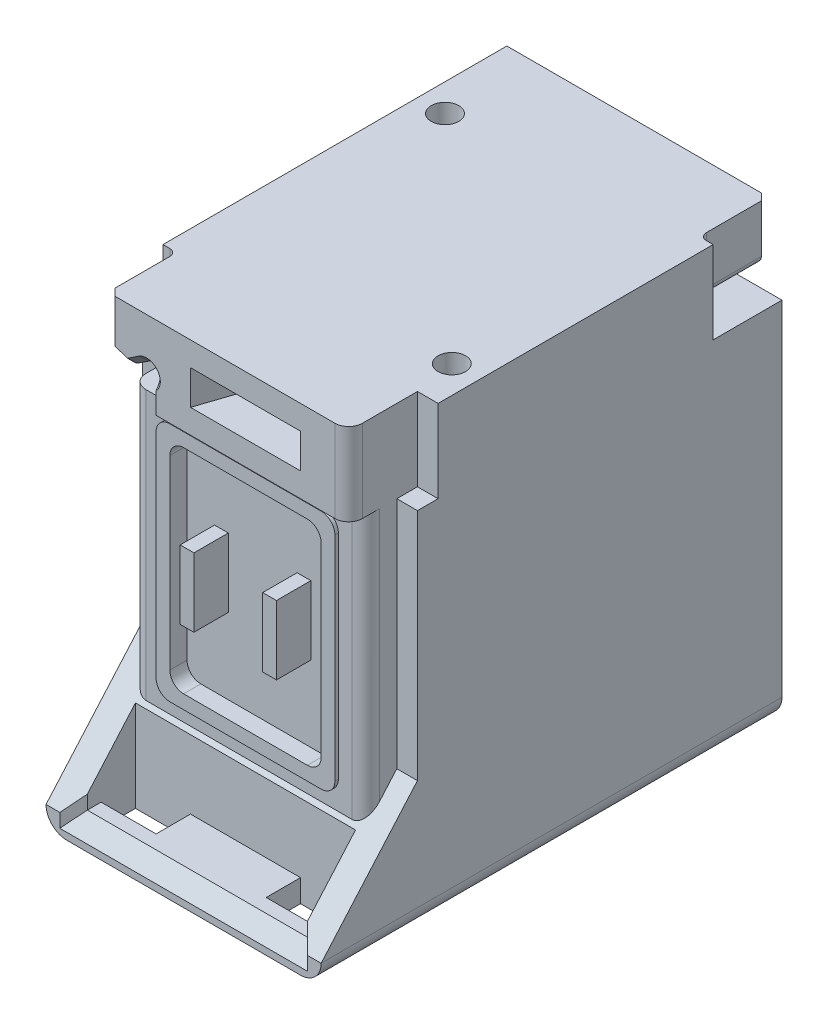
SolidWorks part; units mm, degrees
note: '?' marks a value the reader was unsure of.
ref_plane "Front Plane" through (0, 0, 0) normal (0, 0, 1) x (1, 0, 0)
ref_plane "Top Plane" through (0, 0, 0) normal (0, 1, 0) x (1, 0, 0)
ref_plane "Right Plane" through (0, 0, 0) normal (1, 0, 0) x (0, 0, -1)
sketch "Sketch1" plane through (0, 0, 0) normal (0, 0, 1) x (1, 0, 0)
  line L1 (0, 0) -> (10.16, 0)
  line L2 (0, 0) -> (0, 16.51)
  line L3 (0, 16.51) -> (10.16, 16.51)
  line L4 (10.16, 0) -> (10.16, 16.51)
  dimension "D1" = 16.51
  dimension "D2" = 10.16
extrude "Boss-Extrude1" add sketch "Sketch1" against normal blind 12.7
sketch "Sketch2" plane through (0, 0, 0) normal (-1, 0, 0) x (0, 0, 1)
  line L0 (0, 13.462) -> (0.762, 13.462)
  line L1 (0, 16.51) -> (0, 0) construction
  line L2 (0.762, 13.462) -> (0.762, 4.826)
  line L3 (0, 0) -> (4.318, 0)
  line L4 (4.318, 0) -> (4.318, 0.762)
  line L5 (4.318, 0.762) -> (0.762, 4.826)
  line L6 (0, 0) -> (0, 13.462)
  dimension "D1" = 0.762
  dimension "D2" = 8.636
  dimension "D3" = 3.048
  dimension "D4" = 4.318
  dimension "D5" = 0.762
extrude "Boss-Extrude2" add sketch "Sketch2" against normal blind 10.16
sketch "Sketch3" plane through (0, 0, -12.7) normal (0, 0, -1) x (-1, 0, 0)
  line L0 (-1.016, 4.064) -> (-2.286, 4.064)
  line L1 (-2.286, 4.064) -> (-2.286, 7.112)
  line L2 (-2.286, 7.112) -> (-1.016, 7.112)
  line L3 (-1.016, 7.112) -> (-1.016, 4.064)
  line L4 (0, 16.51) -> (0, 0) construction
  line L5 (0, 0) -> (-10.16, 0) construction
  dimension "D1" = 3.048
  dimension "D2" = 1.27
  dimension "D3" = 1.016
  dimension "D4" = 4.064
extrude "Cut-Extrude1" cut sketch "Sketch3" against normal blind 1.524
sketch "Sketch4" plane through (0, 0, -12.7) normal (0, 0, -1) x (-1, 0, 0)
  line L0 (-10.16, 13.462) -> (-7.874, 13.462)
  line L1 (-10.16, 0) -> (-10.16, 16.51) construction
  line L2 (-10.16, 13.462) -> (-10.16, 16.51)
  line L3 (-7.874, 13.462) -> (-7.874, 14.732)
  line L4 (-10.16, 16.51) -> (-9.652, 16.51)
  line L5 (-10.16, 16.51) -> (0, 16.51) construction
  line L6 (-9.652, 16.51) -> (-9.652, 14.732)
  line L7 (-9.652, 14.732) -> (-9.3225, 14.732) construction
  line L8 (-9.4681, 14.4879) -> (-9.2239, 14.4178)
  line L9 (-9.0453, 14.4323) -> (-8.3564, 14.758)
  arc A0 (-9.652, 14.732) -> (-9.4681, 14.4879) centre (-9.398, 14.732) ccw
  arc A1 (-9.2239, 14.4178) -> (-9.0453, 14.4323) centre (-9.1539, 14.6619) ccw
  arc A2 (-8.3564, 14.758) -> (-7.874, 14.732) centre (-8.1393, 14.2988) cw
  dimension "D6" = 0.254
  dimension "D7" = 0.254
  dimension "D8" = 0.254
  dimension "D10" = 0.508
  dimension "D1" = 3.048
  dimension "D2" = 2.286
  dimension "D3" = 1.27
  dimension "D4" = 0.508
  dimension "D5" = 1.778
  dimension "D9" = 0.762
extrude "Cut-Extrude2" cut sketch "Sketch4" against normal blind 2.54
sketch "Sketch6" plane through (0, 0, 0) normal (0, -1, 0) x (-1, 0, 0)
  line L0 (-1.016, -2.032) -> (-1.016, -3.302)
  line L1 (-1.016, -3.302) -> (-3.048, -3.302)
  line L2 (-3.048, -3.302) -> (-3.048, -2.032)
  line L3 (-3.048, -2.032) -> (-1.016, -2.032)
  line L4 (-10.16, -4.318) -> (0, -4.318) construction
  line L5 (0, 12.7) -> (0, -4.318) construction
  line L6 (-5.08, -4.318) -> (-5.08, 12.7) construction
  line L7 (0, 12.7) -> (-10.16, 12.7) construction
  line L8 (-7.112, -3.302) -> (-7.112, -2.032)
  line L9 (-9.144, -3.302) -> (-7.112, -3.302)
  line L10 (-9.144, -2.032) -> (-9.144, -3.302)
  line L11 (-7.112, -2.032) -> (-9.144, -2.032)
  dimension "D1" = 1.27
  dimension "D2" = 2.032
  dimension "D3" = 1.016
  dimension "D4" = 1.016
extrude "Cut-Extrude5" cut sketch "Sketch6" against normal through all
sketch "Sketch8" plane through (0, 0, 2.032) normal (0, 0, 1) x (1, 0, 0)
  line L0 (1.016, 3.3746) -> (9.144, 3.3746)
  line L1 (3.048, 3.3746) -> (1.016, 3.3746) construction
  line L2 (9.144, 3.3746) -> (9.144, 1.3426)
  line L3 (9.144, 1.3426) -> (1.016, 1.3426)
  line L4 (1.016, 1.3426) -> (1.016, 3.3746)
  line L5 (1.016, 3.3746) -> (1.016, 0) construction
  dimension "D1" = 2.032
extrude "Cut-Extrude6" cut sketch "Sketch8" along normal blind 2.54
sketch3d "3DSketch3"
  line L0 (0.508, 0.762, 4.318) -> (0.508, 0.254, 4.318)
  line L1 (10.16, 0.762, 4.318) -> (0, 0.762, 4.318) construction
  line L2 (0, 0, 4.318) -> (0, 0.762, 4.318) construction
  line L3 (0.508, 0.762, 4.318) -> (1.016, 1.3426, 3.81)
  line L5 (1.016, 1.3426, 3.81) -> (1.016, 0.8346, 3.81)
  line L6 (1.016, 0.8346, 3.81) -> (0.508, 0.254, 4.318)
  dimension "D1" = 0.508
  dimension "D2" = 0.508
extrude "Cut-Extrude7" cut sketch "3DSketch3" along direction (-1, 0, 0) on the side against the normal blind 8.128
sketch "Sketch10" plane through (0, 0, 3.81) normal (0, 0, 1) x (1, 0, 0)
  line L1 (1.016, 0.8346) -> (9.144, 0.8346)
  line L2 (1.016, 0.8346) -> (1.016, 1.3426)
  line L3 (1.016, 1.3426) -> (9.144, 1.3426)
  line L4 (9.144, 0.8346) -> (9.144, 1.3426)
extrude "Cut-Extrude8" cut sketch "Sketch10" against normal up to surface (1.778 mm away)
sketch3d "3DSketch6"
  line L0 (9.652, 0.762, 4.318) -> (9.144, 1.3426, 3.81)
  line L1 (10.16, 0.762, 4.318) -> (8.636, 0.762, 4.318) construction
  line L2 (9.144, 1.3426, 3.81) -> (9.144, 0.8346, 3.81)
  line L3 (9.652, 0.762, 4.318) -> (9.652, 0.254, 4.318)
  line L4 (9.652, 0.254, 4.318) -> (9.144, 0.8346, 3.81)
  dimension "D1" = 0.508
extrude "Cut-Extrude9" cut sketch "3DSketch6" along direction (-1, 0, 0) on the side of the normal blind 1.778
sketch "Sketch12" plane through (0, 13.462, 0) normal (0, 1, 0) x (1, 0, 0)
  line L0 (0.762, -0.762) -> (0.762, -1.905)
  line L1 (10.16, -0.762) -> (0, -0.762) construction
  line L2 (0.762, -1.905) -> (9.398, -1.905)
  line L3 (9.398, -1.905) -> (9.398, -0.762)
  line L4 (9.398, -0.762) -> (0.762, -0.762)
  dimension "D1" = 1.143
  dimension "D2" = 0.762
  dimension "D3" = 0.762
extrude "Boss-Extrude3" add sketch "Sketch12" against normal up to surface (9.9423 mm away)
sketch "Sketch13" plane through (0, 0, 1.905) normal (0, 0, 1) x (1, 0, 0)
  line L0 (0.762, 8.4909) -> (9.398, 8.4909) construction
  line L1 (0.762, 3.5197) -> (0.762, 13.462) construction
  line L2 (9.398, 3.5197) -> (9.398, 13.462) construction
  line L3 (5.08, 13.462) -> (5.08, 3.5197) construction
  line L4 (0.762, 13.462) -> (9.398, 13.462) construction
  line L5 (9.398, 3.5197) -> (0.762, 3.5197) construction
  line L7 (2.794, 12.4279) -> (7.366, 12.4279)
  line L8 (2.286, 11.9199) -> (2.286, 5.0619)
  line L9 (2.794, 4.5539) -> (7.366, 4.5539)
  line L10 (7.874, 11.9199) -> (7.874, 5.0619)
  line L11 (2.286, 12.4279) -> (7.874, 4.5539) construction
  line L12 (2.286, 4.5539) -> (7.874, 12.4279) construction
  arc A0 (2.286, 5.0619) -> (2.794, 4.5539) centre (2.794, 5.0619) ccw
  arc A1 (7.366, 4.5539) -> (7.874, 5.0619) centre (7.366, 5.0619) ccw
  arc A2 (7.366, 12.4279) -> (7.874, 11.9199) centre (7.366, 11.9199) cw
  arc A3 (2.794, 12.4279) -> (2.286, 11.9199) centre (2.794, 11.9199) ccw
  point P12 (5.08, 8.4909)
  dimension "D2" = 0.508
  dimension "D1" = 5.588
extrude "Cut-Extrude10" cut sketch "Sketch13" against normal blind 0.508
sketch "Sketch14" plane through (0, 0, 1.905) normal (0, 0, 1) x (1, 0, 0)
  line L0 (0.762, 8.4909) -> (9.398, 8.4909) construction
  line L1 (0.762, 3.5197) -> (0.762, 13.462) construction
  line L2 (9.398, 3.5197) -> (9.398, 13.462) construction
  line L3 (5.08, 13.462) -> (5.08, 3.5197) construction
  line L4 (0.762, 13.462) -> (9.398, 13.462) construction
  line L5 (9.398, 3.5197) -> (0.762, 3.5197) construction
  line L6 (7.366, 12.4279) -> (2.794, 12.4279) construction
  line L7 (2.286, 4.0459) -> (7.874, 4.0459)
  line L8 (1.778, 4.5539) -> (1.778, 12.4279)
  line L9 (2.286, 12.9359) -> (7.874, 12.9359)
  line L10 (8.382, 4.5539) -> (8.382, 12.4279)
  line L11 (2.1862, 4.5953) -> (8.382, 12.9359) construction
  line L12 (1.778, 12.9359) -> (8.382, 4.0459) construction
  line L13 (2.286, 11.9199) -> (2.286, 5.0619) construction
  line L15 (2.794, 12.4279) -> (7.366, 12.4279)
  line L16 (2.286, 11.9199) -> (2.286, 5.0619)
  line L17 (2.794, 4.5539) -> (7.366, 4.5539)
  line L18 (7.874, 11.9199) -> (7.874, 5.0619)
  line L19 (2.286, 12.4279) -> (7.874, 4.5539) construction
  line L20 (2.286, 4.5539) -> (7.874, 12.4279) construction
  arc A0 (2.286, 4.0459) -> (1.778, 4.5539) centre (2.286, 4.5539) cw
  arc A1 (7.874, 4.0459) -> (8.382, 4.5539) centre (7.874, 4.5539) ccw
  arc A2 (7.874, 12.9359) -> (8.382, 12.4279) centre (7.874, 12.4279) cw
  arc A3 (1.778, 12.4279) -> (2.286, 12.9359) centre (2.286, 12.4279) cw
  arc A4 (2.794, 12.4279) -> (2.286, 11.9199) centre (2.794, 11.9199) ccw
  arc A5 (7.366, 12.4279) -> (7.874, 11.9199) centre (7.366, 11.9199) cw
  arc A6 (7.366, 4.5539) -> (7.874, 5.0619) centre (7.366, 5.0619) ccw
  arc A7 (2.286, 5.0619) -> (2.794, 4.5539) centre (2.794, 5.0619) ccw
  point P12 (5.08, 8.4909)
  point P33 (5.08, 8.4909)
  dimension "D4" = 0.508
  dimension "D1" = 0.508
  dimension "D2" = 0.508
extrude "Boss-Extrude4" add sketch "Sketch14" along normal blind 0.127
sketch "Sketch16" plane through (0, 0, 1.397) normal (0, 0, 1) x (1, 0, 0)
  line L0 (2.286, 11.9199) -> (2.286, 5.0619) construction
  line L1 (3.302, 9.8879) -> (3.81, 9.8879)
  line L2 (3.302, 9.8879) -> (3.302, 7.3479)
  line L3 (3.302, 7.3479) -> (3.81, 7.3479)
  line L4 (3.81, 9.8879) -> (3.81, 7.3479)
  line L5 (3.302, 9.8879) -> (3.81, 7.3479) construction
  line L6 (3.302, 7.3479) -> (3.81, 9.8879) construction
  line L7 (2.794, 4.5539) -> (7.366, 4.5539) construction
  line L9 (5.08, 12.4279) -> (5.08, 4.5539) construction
  line L10 (7.366, 12.4279) -> (2.794, 12.4279) construction
  line L11 (6.858, 9.8879) -> (6.35, 9.8879)
  line L12 (6.858, 9.8879) -> (6.858, 7.3479)
  line L13 (6.858, 7.3479) -> (6.35, 7.3479)
  line L14 (6.35, 9.8879) -> (6.35, 7.3479)
  point P0 (3.556, 8.6179)
  dimension "D1" = 0.508
  dimension "D2" = 2.54
  dimension "D3" = 1.016
  dimension "D4" = 2.794
extrude "Boss-Extrude5" add sketch "Sketch16" along normal blind 1.27
sketch "Sketch17" plane through (0, 16.51, 0) normal (0, 1, 0) x (1, 0, 0)
  line L0 (0, 12.7) -> (10.16, 0) construction
sketch "Sketch18" plane through (0, 0, 0) normal (0, 0, 1) x (1, 0, 0)
  line L0 (9.398, 16.51) -> (9.398, 13.462)
  line L1 (10.16, 16.51) -> (0, 16.51) construction
  line L2 (10.16, 13.462) -> (0, 13.462) construction
  line L3 (9.398, 13.462) -> (2.286, 13.462)
  line L4 (2.286, 13.462) -> (2.286, 16.51)
  line L5 (2.286, 16.51) -> (9.398, 16.51)
  line L6 (0, 16.51) -> (0, 13.462) construction
  dimension "D1" = 0.762
  dimension "D2" = 2.286
extrude "Boss-Extrude6" add sketch "Sketch18" along normal blind 2.54
sketch "Sketch19" plane through (0, 0, 2.54) normal (0, 0, 1) x (1, 0, 0)
  line L0 (9.398, 14.986) -> (7.112, 14.986) construction
  line L1 (9.398, 13.462) -> (9.398, 16.51) construction
  line L2 (7.112, 14.986) -> (4.064, 14.986) construction
  line L3 (4.064, 15.621) -> (7.112, 15.621)
  line L4 (4.064, 15.621) -> (4.064, 14.351)
  line L5 (7.112, 15.621) -> (7.112, 14.351)
  line L6 (4.064, 14.351) -> (7.112, 14.351)
  line L7 (4.064, 15.621) -> (7.112, 14.351) construction
  line L8 (7.112, 15.621) -> (4.064, 14.351) construction
  point P6 (5.588, 14.986)
  dimension "D1" = 2.286
  dimension "D2" = 3.048
  dimension "D3" = 1.27
extrude "Cut-Extrude11" cut sketch "Sketch19" against normal blind 1.524
sketch3d "3DSketch8"
  line L0 (4.064, 15.621, 1.016) -> (3.556, 15.621, 2.54)
  line L1 (7.112, 15.621, 1.016) -> (4.064, 15.621, 1.016) construction
  line L2 (4.064, 15.621, 1.016) -> (4.064, 14.351, 1.016) construction
  line L5 (4.064, 15.621, 2.54) -> (3.4133, 15.621, 2.54) construction
  line L6 (4.064, 15.621, 1.016) -> (4.064, 14.351, 1.016)
  line L7 (4.064, 14.351, 1.016) -> (7.112, 14.351, 1.016) construction
  line L8 (4.064, 14.351, 1.016) -> (3.556, 14.351, 2.54)
  line L9 (3.556, 14.351, 2.54) -> (3.556, 15.621, 2.54)
  line L10 (4.064, 14.351, 2.54) -> (3.556, 14.351, 2.54) construction
  dimension "D1" = 0.508
  dimension "D2" = 0.508
extrude "Cut-Extrude12" cut sketch "3DSketch8" along direction (1, 0, 0) on the side against the normal blind 1.524
sketch "Sketch21" plane through (0, 0, 1.016) normal (0, 0, 1) x (1, 0, 0)
  line L0 (5.588, 14.351) -> (5.588, 15.621) construction
  line L1 (4.064, 14.351) -> (7.112, 14.351) construction
  line L2 (7.112, 15.621) -> (4.064, 15.621) construction
ref_plane "Plane1" through (5.588, 0, 0) normal (1, 0, 0) x (0, 1, 0)
mirror "Mirror1" about plane through (5.588, 0, 0) normal (1, 0, 0) of "Cut-Extrude12"
sketch "Sketch22" plane through (0, 16.51, 0) normal (0, 1, 0) x (1, 0, 0)
  line L0 (10.16, 0) -> (9.398, 0) construction
  line L1 (9.398, -2.54) -> (9.398, 0) construction
  line L2 (9.652, 12.7) -> (0, 12.7) construction
  line L3 (0, 12.7) -> (0, 0) construction
  circle A0 centre (9.144, 1.524) radius 0.508
  circle A1 centre (1.016, 9.398) radius 0.508
  dimension "D3" = 1.016
  dimension "D6" = 1.016
  dimension "D1" = 1.524
  dimension "D2" = 0.254
  dimension "D4" = 3.302
  dimension "D5" = 1.016
extrude "Cut-Extrude13" cut sketch "Sketch22" against normal blind 0.762
sketch "Sketch23" plane through (0, 0, 0) normal (0, 0, 1) x (1, 0, 0)
  line L0 (2.286, 16.51) -> (0.508, 16.51)
  line L1 (2.286, 16.51) -> (2.286, 13.462) construction
  line L2 (0, 16.51) -> (10.16, 16.51) construction
  line L3 (2.286, 16.51) -> (0, 16.51) construction
  line L4 (0.508, 16.51) -> (0.508, 14.9151)
  line L5 (2.286, 14.478) -> (2.286, 16.51)
  line L6 (2.286, 14.478) -> (2.032, 14.986)
  line L7 (2.032, 14.986) -> (1.3734, 14.5469)
  line L8 (1.1521, 14.5173) -> (0.6817, 14.6741)
  arc A0 (0.508, 14.9151) -> (0.6817, 14.6741) centre (0.762, 14.9151) ccw
  arc A1 (1.3734, 14.5469) -> (1.1521, 14.5173) centre (1.2325, 14.7582) cw
  point P15 (0.508, 14.732)
  point P18 (1.27, 14.478)
  dimension "D8" = 0.254
  dimension "D1" = 1.778
  dimension "D2" = 1.778
  dimension "D3" = 2.032
  dimension "D4" = 0.508
  dimension "D5" = 0.254
  dimension "D6" = 0.762
  dimension "D7" = 0.508
extrude "Boss-Extrude8" add sketch "Sketch23" along normal blind 2.54 contours L7 A1 L8 A0 L4 L0 L5 L6
fillet "Fillet1" radius 0.762 2 edges at (10.16, 0, -4.191) (0, 0, -4.191)
fillet "Fillet2" radius 0.508 2 edges at (0.762, 8.4909, 1.905) (9.398, 8.4909, 1.905)
fillet "Fillet3" radius 0.508 1 edges at (9.398, 14.986, 2.54)
fillet "Fillet4" radius 0.254 1 edges at (2.032, 14.986, 1.27)
chamfer "Chamfer2" distance 0.254 angle 45 6 edges at (1.9987, 14.8605, 2.54) (1.583, 14.6867, 2.54) (1.2662, 14.5065, 2.54) (0.9169, 14.5957, 2.54) (0.5559, 14.7666, 2.54) (0.508, 15.7125, 2.54)
fillet "Fillet5" radius 0.254 8 edges at (2.2233, 14.6033, 0) (1.9987, 14.8605, 0) (1.583, 14.6867, 0) (1.2662, 14.5065, 0) (0.9169, 14.5957, 0) (0.5559, 14.7666, 0) (0.508, 15.7125, 0) (2.286, 13.97, 0)
chamfer "Chamfer3" distance 0.254 angle 45 6 edges at (8.1119, 14.806, -12.7) (8.7008, 14.5952, -12.7) (9.1333, 14.4088, -12.7) (9.346, 14.4528, -12.7) (9.6009, 14.5792, -12.7) (9.652, 15.621, -12.7)
fillet "Fillet6" radius 0.254 1 edges at (7.874, 14.732, -11.303)
fillet "Fillet8" radius 0.254 8 edges at (7.874, 14.0073, -10.16) (7.9445, 14.7281, -10.16) (8.2395, 14.7968, -10.16) (8.7008, 14.5952, -10.16) (9.1333, 14.4088, -10.16) (9.346, 14.4528, -10.16) (9.6009, 14.5792, -10.16) (9.652, 15.621, -10.16)
sketch "Sketch24" plane through (0, 0, 2.667) normal (0, 0, 1) x (1, 0, 0)
  point P0 (3.556, 8.6179)
  point P1 (6.604, 8.6179)
sketch "0_0_Point" plane through (0, 0, 2.667) normal (0, 0, 1) x (1, 0, 0)
  point P0 (3.556, 8.6179)
other "0_0" parameters "Diameter"=2, "StubLength"=2
ref_axis "Axis1" through (3.556, 8.6179, 12.667) along (0, 0, -1)?
sketch "0_1_Point" plane through (0, 0, 2.667) normal (0, 0, 1) x (1, 0, 0)
  point P0 (6.604, 8.6179)
other "0_1" parameters "Diameter"=2, "StubLength"=2
ref_axis "Axis2" through (6.604, 8.6179, 12.667) along (0, 0, -1)?
